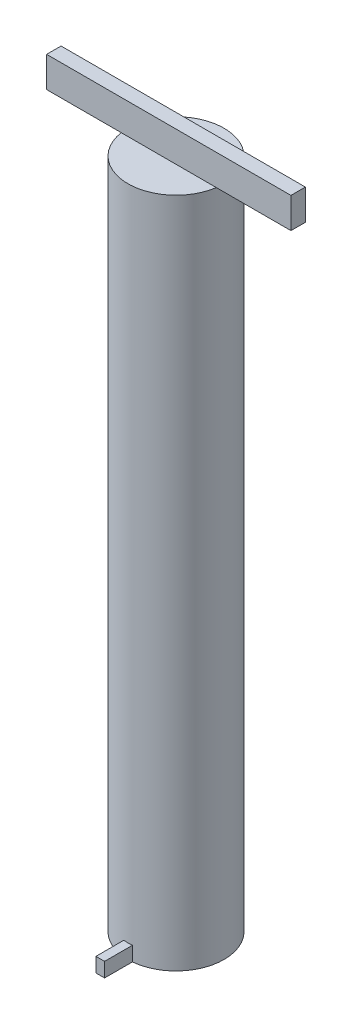
SolidWorks part; units mm, degrees
ref_plane "Front Plane" through (0, 0, 0) normal (0, 0, 1) x (1, 0, 0)
ref_plane "Top Plane" through (0, 0, 0) normal (0, 1, 0) x (1, 0, 0)
ref_plane "Right Plane" through (0, 0, 0) normal (1, 0, 0) x (0, 0, -1)
sketch "Sketch1" plane through (0, 0, 0) normal (0, 1, 0) x (1, 0, 0)
  circle A0 centre (0, 0) radius 10
  dimension "D1" = 20
extrude "Boss-Extrude1" add sketch "Sketch1" along normal blind 139.7
sketch "Sketch3" plane through (0, 0, 0) normal (0, -1, 0) x (1, 0, 0)
  line L1 (-0.9, 15.75) -> (0.9, 15.75)
  line L2 (-0.9, 15.75) -> (-0.9, 9.3548)
  line L4 (0.9, 15.75) -> (0.9, 9.3548)
  arc A0 (0.9, 9.3548) -> (-0.9, 9.3548) centre (0, 0) ccw
  dimension "D1" = 0.9
  dimension "D3" = 15.75
extrude "Boss-Extrude2" add sketch "Sketch3" against normal blind 3
sketch "Sketch4" plane through (0, 139.7, 0) normal (0, 1, 0) x (1, 0, 0)
  line L1 (-25.4, 1.5) -> (25.4, 1.5)
  line L2 (-25.4, 1.5) -> (-25.4, -1.5)
  line L3 (-25.4, -1.5) -> (25.4, -1.5)
  line L4 (25.4, 1.5) -> (25.4, -1.5)
  point P4 (-25.4, 0)
  point P5 (0, 1.5)
  dimension "D1" = 50.8
  dimension "D2" = 3
extrude "Boss-Extrude3" add sketch "Sketch4" along normal blind 6.35
sketch "Sketch5" plane through (0, 0, 0) normal (0, -1, 0) x (1, 0, 0)
  circle A0 centre (0, 0) radius 8
  dimension "D1" = 16
extrude "Cut-Extrude1" cut sketch "Sketch5" against normal blind 2.54
